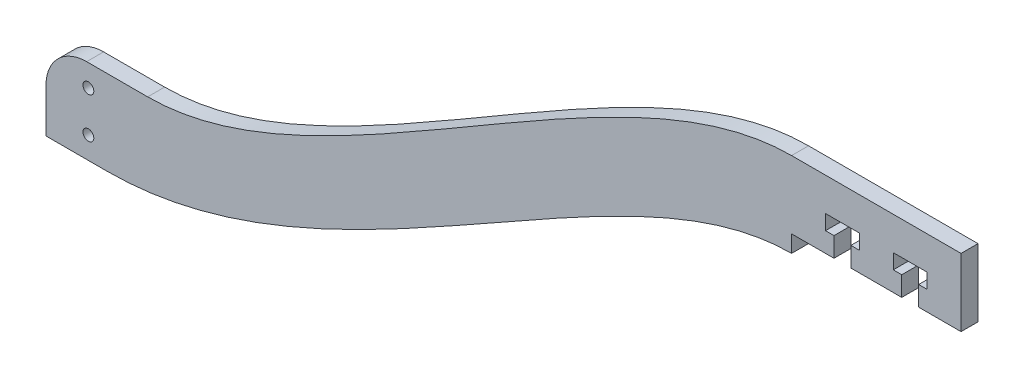
SolidWorks part; units mm, degrees
ref_plane "Front Plane" through (0, 0, 0) normal (0, 0, 1) x (1, 0, 0)
ref_plane "Top Plane" through (0, 0, 0) normal (0, 1, 0) x (1, 0, 0)
ref_plane "Right Plane" through (0, 0, 0) normal (1, 0, 0) x (0, 0, -1)
sketch "Sketch1" plane through (0, 0, 0) normal (0, 0, 1) x (1, 0, 0)
  line L1 (-139.7, -42.545) -> (-139.7, -50.8)
  line L2 (-71.502, -34.925) -> (-125.3505, -34.925) construction
  line L3 (0, 0) -> (0, 3.175)
  line L4 (0, 3.175) -> (7.9375, 3.175)
  line L5 (31.75, 3.175) -> (31.75, 15.875)
  line L6 (31.75, 15.875) -> (0, 15.875)
  line L7 (0, -1000) -> (0, 49000) construction
  line L8 (9.525, -988.6477) -> (9.525, 49011.3523) construction
  line L9 (22.225, -989.9681) -> (22.225, 49010.0319) construction
  line L10 (7.9375, 3.175) -> (7.9375, 6.858)
  line L11 (7.9375, 6.858) -> (6.35, 6.858)
  line L12 (6.35, 6.858) -> (6.35, 9.652)
  line L13 (6.35, 9.652) -> (12.7, 9.652)
  line L14 (12.7, 9.652) -> (12.7, 6.858)
  line L15 (12.7, 6.858) -> (11.1125, 6.858)
  line L16 (11.1125, 6.858) -> (11.1125, 3.175)
  line L17 (11.1125, 3.175) -> (20.6375, 3.175)
  line L18 (20.6375, 3.175) -> (20.6375, 6.858)
  line L19 (20.6375, 6.858) -> (19.05, 6.858)
  line L20 (19.05, 6.858) -> (19.05, 9.652)
  line L21 (19.05, 9.652) -> (25.4, 9.652)
  line L22 (25.4, 9.652) -> (25.4, 6.858)
  line L23 (25.4, 6.858) -> (23.8125, 6.858)
  line L24 (23.8125, 6.858) -> (23.8125, 3.175)
  line L25 (23.8125, 3.175) -> (31.75, 3.175)
  line L26 (-131.7625, -1027.5749) -> (-131.7625, 48972.4251) construction
  line L27 (-128.27, -50.8) -> (-139.7, -50.8)
  line L28 (-120.65, -34.925) -> (-132.08, -34.925)
  line L29 (-127, -288.925) -> (-120.65, -34.925) construction
  line L30 (-71.502, -50.8) -> (-125.3505, -50.8) construction
  line L32 (26.7231, 15.875) -> (-26.7231, 15.875) construction
  line L33 (26.3977, 0) -> (-26.3989, 0) construction
  circle A0 centre (-131.7625, -39.0525) radius 1.016
  circle A1 centre (-131.7625, -46.6725) radius 1.016
  arc A2 (-132.08, -34.925) -> (-139.7, -42.545) centre (-132.08, -42.545) ccw
  spline S0 degree 3 poles (-120.65, -34.925) (-86.9947, -34.925) (-33.4039, 15.875) (0, 15.875) knots 0 0 0 0 1 1 1 1
  spline S1 degree 3 poles (-128.27, -50.8) (-84.7243, -50.8) (-32.9979, 0) (0, 0) knots 0 0 0 0 1 1 1 1
  point P23 (9.525, 9.652)
  point P31 (22.225, 9.652)
  point P48 (-139.7, -34.925)
  dimension "D14" = 2.032
  dimension "D17" = 7.62
  dimension "D1" = 3.175
  dimension "D2" = 15.875
  dimension "D3" = 15.875
  dimension "D4" = 139.7
  dimension "D5" = 31.75
  dimension "D6" = 9.525
  dimension "D7" = 12.7
  dimension "D8" = 6.35
  dimension "D9" = 2.794
  dimension "D10" = 6.477
  dimension "D11" = 3.175
  dimension "D12" = 50.8
  dimension "D13" = 7.9375
  dimension "D15" = 4.1275
  dimension "D16" = 7.62
extrude "Boss-Extrude1" add sketch "Sketch1" along normal blind 3.175
